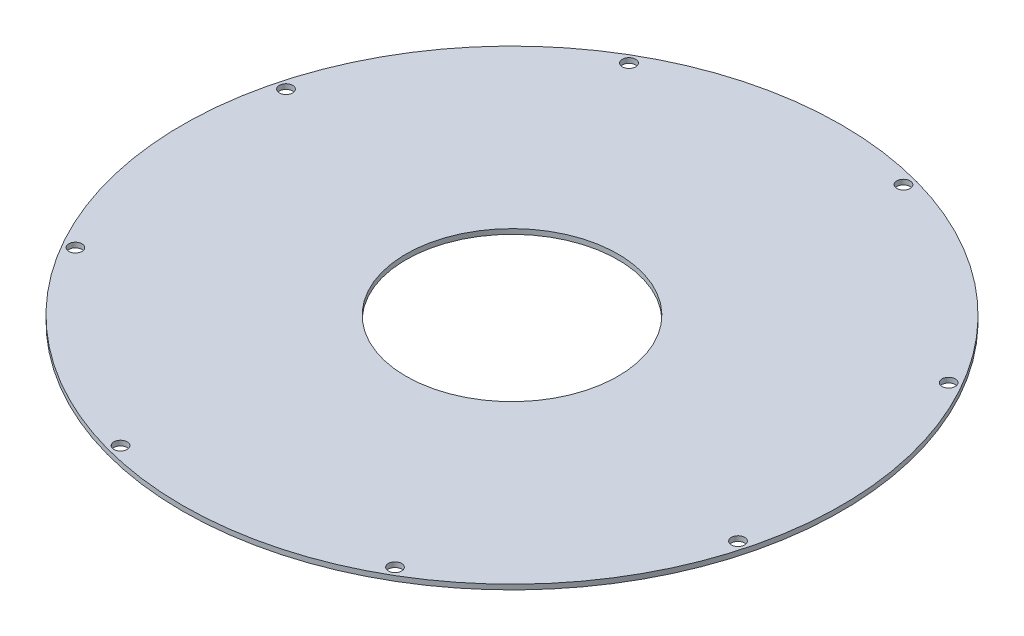
SolidWorks part; units mm, degrees
material "Thornel Mat VMA"
ref_plane "Front Plane" through (0, 0, 0) normal (0, 0, 1) x (1, 0, 0)
ref_plane "Top Plane" through (0, 0, 0) normal (0, 1, 0) x (1, 0, 0)
ref_plane "Right Plane" through (0, 0, 0) normal (1, 0, 0) x (0, 0, -1)
sketch "Sketch1" plane through (0, 0, 0) normal (0, 1, 0) x (1, 0, 0)
  circle A0 centre (0, 0) radius 32
  circle A1 centre (0, 0) radius 99.5
  dimension "D1" = 64
  dimension "D2" = 199
extrude "Base" add sketch "Sketch1" along normal mid plane 1.5
sketch "Sketch2" plane through (0, 0.75, 0) normal (0, 1, 0) x (1, 0, 0)
  line L0 (24.976, 93.2118) -> (25.7525, 96.1096) construction
  line L1 (24.976, 93.2118) -> (0, 0) construction
  line L2 (0, 0) -> (0, 99.5) construction
  circle A0 centre (24.976, 93.2118) radius 2
  circle A2 centre (0, 0) radius 99.5 construction
  dimension "D1" = 4
  dimension "D2" = 3
  dimension "D3" = 15
extrude "Structural Hole" cut sketch "Sketch2" against normal through all
pattern_circular "Structural Hole Pattern" count 8 over 360 about axis through (0, 0.75, 0) along (0, -1, 0) of "Structural Hole" reverse direction yes
equation "\"lift_fan_diameter\"=64"
equation "\"D1@Sketch1\"=\"lift_fan_diameter\""
equation "\"outer_diameter\"=199"
equation "\"D2@Sketch1\"=\"outer_diameter\""
equation "\"bolt_diameter\"=4"
equation "\"D1@Sketch2\"=\"bolt_diameter\""
equation "\"wall_thickness\"=3"
equation "\"D2@Sketch2\"=\"wall_thickness\""
